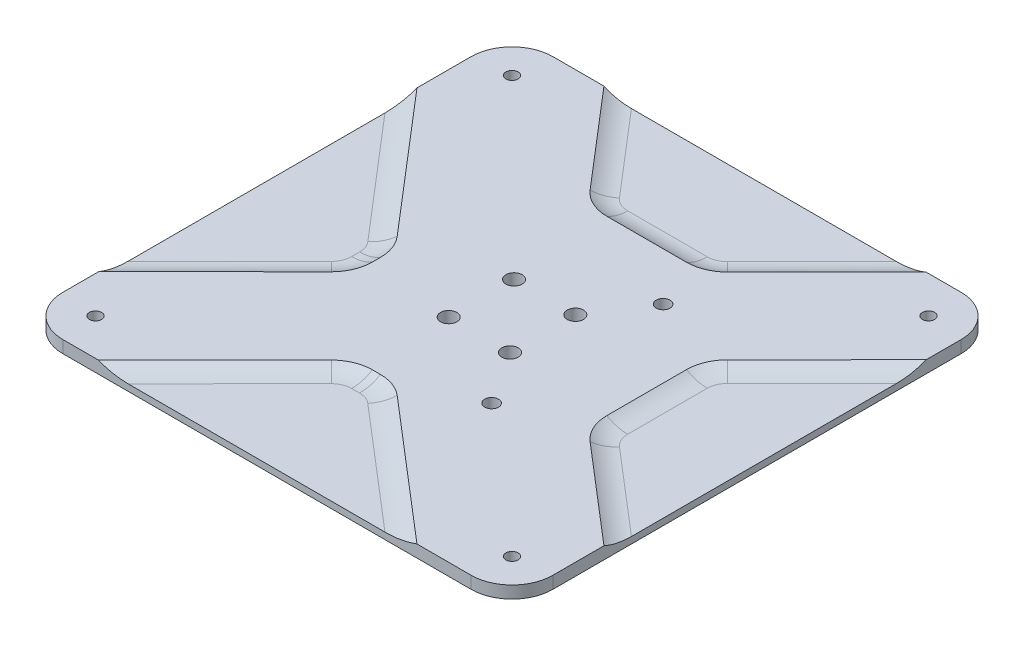
SolidWorks part; units mm, degrees
material "ABS"
ref_plane "Alzado" through (0, 0, 0) normal (0, 0, 1) x (1, 0, 0)
ref_plane "Planta" through (0, 0, 0) normal (0, 1, 0) x (1, 0, 0)
ref_plane "Vista lateral" through (0, 0, 0) normal (1, 0, 0) x (0, 0, -1)
sketch "Sketch1" plane through (0, 0, 0) normal (0, 1, 0) x (1, 0, 0)
  line L1 (-7.5, -8) -> (7.5, -8) construction
  line L2 (-7.5, -8) -> (-7.5, 8) construction
  line L3 (-7.5, 8) -> (7.5, 8) construction
  line L4 (7.5, -8) -> (7.5, 8) construction
  line L5 (-7.5, -8) -> (7.5, 8) construction
  line L6 (-7.5, 8) -> (7.5, -8) construction
  line L7 (-60, -60) -> (60, -60)
  line L8 (-60, -60) -> (-60, 60)
  line L9 (-60, 60) -> (60, 60)
  line L10 (60, -60) -> (60, 60)
  circle A0 centre (-7.5, -8) radius 2
  circle A1 centre (7.5, 8) radius 2
  circle A2 centre (7.5, -8) radius 2
  circle A3 centre (-7.5, 8) radius 2
  point P0 (0, 0)
  point P10 (0, 0)
  point P16 (-60, 0)
  point P17 (0, -60)
  dimension "D3" = 4
  dimension "D1" = 16
  dimension "D2" = 15
  dimension "D4" = 120
  dimension "D5" = 120
extrude "Boss-Extrude1" add sketch "Sketch1" along normal blind 3
fillet "Fillet1" radius 10 4 edges at (-60, 1.5, -60) (60, 1.5, -60) (60, 1.5, 60) (-60, 1.5, 60)
sketch "Sketch2" plane through (0, 3, 0) normal (0, 1, 0) x (1, 0, 0)
  line L0 (50, 60) -> (-50, 60) construction
  line L1 (-60, 50) -> (-60, -50) construction
  circle A0 centre (-51, 51) radius 1.5
  dimension "D1" = 3
  dimension "D2" = 9
  dimension "D3" = 9
extrude "Cut-Extrude1" cut sketch "Sketch2" against normal through all
mirror "Mirror3" about plane through (0, 0, 0) normal (0, 0, 1) of "Cut-Extrude1" second plane through (0, 0, 0) second plane normal (1, 0, 0)
sketch "Sketch3" plane through (0, 3, 0) normal (0, 1, 0) x (1, 0, 0)
  line L0 (16, 21) -> (16, -21) construction
  circle A2 centre (16, 21) radius 1.7
  circle A3 centre (16, -21) radius 1.7
  point P4 (16, 0)
  dimension "D2" = 42
  dimension "D1" = 3.4
  dimension "D3" = 16
extrude "Cut-Extrude2" cut sketch "Sketch3" against normal through all
sketch "Sketch5" plane through (0, 3, 0) normal (0, 1, 0) x (1, 0, 0)
  line L0 (60, 41.4316) -> (32.7473, 14.122)
  line L1 (60, -50) -> (60, 50) construction
  line L2 (32.7473, 14.122) -> (32.7473, -14.122)
  line L3 (32.7473, -14.122) -> (60, -37.4814)
  line L4 (0, 60) -> (0, -60) construction
  line L5 (60, 41.4316) -> (60, -37.4814)
  line L6 (-50, -60) -> (50, -60) construction
  line L7 (36.7283, -60) -> (0, -28.5186)
  line L8 (0, -28.5186) -> (-9.8043, -28.5186)
  line L9 (-9.8043, -28.5186) -> (-41.22, -60)
  line L10 (-60, 0) -> (60, 0) construction
  line L11 (-41.22, -60) -> (36.7283, -60)
  line L12 (16, -21) -> (51, -51) construction
  line L13 (16, 21) -> (16, -21) construction
  line L14 (0, -28.5186) -> (9.8043, -28.5186) construction
  line L15 (9.8043, -28.5186) -> (9.8043, -36.9222) construction
  line L16 (60, -37.4814) -> (36.7283, -60) construction
  line L17 (57.0711, 57.0711) -> (-58.3189, -58.3189) construction
  line L18 (-60, -41.22) -> (-60, 36.7283)
  line L19 (-28.5186, -9.8043) -> (-60, -41.22)
  line L20 (-28.5186, 0) -> (-28.5186, -9.8043)
  line L21 (-60, 36.7283) -> (-28.5186, 0)
  line L22 (41.4316, 60) -> (-37.4814, 60)
  line L23 (-14.122, 32.7473) -> (-37.4814, 60)
  line L24 (14.122, 32.7473) -> (-14.122, 32.7473)
  line L25 (41.4316, 60) -> (14.122, 32.7473)
  arc A0 (60, 50) -> (50, 60) centre (50, 50) ccw construction
  point P18 (48.3642, -48.7407)
  point P20 (32.7473, 0)
extrude "Cut-Extrude3" cut sketch "Sketch5" against normal blind 1.4
fillet "Fillet2" radius 10 8 edges at (-28.5186, 2.3, 9.8043) (-28.5186, 2.3, 0) (-14.122, 2.3, -32.7473) (14.122, 2.3, -32.7473) (32.7473, 2.3, 14.122) (32.7473, 2.3, -14.122) (0, 2.3, 28.5186) (-9.8043, 2.3, 28.5186)
fillet "Fillet3" radius 10 20 edges at (-45.7274, 1.6, 26.9773) (-29.2818, 1.6, 9.4877) (-28.5186, 1.6, 4.6776) (-45.463, 1.6, -19.7685) (19.7685, 1.6, 45.463) (-0.2298, 1.6, 29.1397) (-4.6776, 1.6, 28.5186) (-26.9773, 1.6, 45.7274) (-27.2983, 1.6, -48.1197) (-13.7012, 1.6, -33.6622) (29.2407, 1.6, -47.8344) (13.808, 1.6, -33.5065) (48.1197, 1.6, 27.2983) (33.6622, 1.6, 13.7012) (32.7473, 1.6, -0.2317) (33.5065, 1.6, -13.808) (-29.1397, 1.6, 0.2298) (-9.4877, 1.6, 29.2818) (0.2317, 1.6, -32.7473) (47.8344, 1.6, -29.2407)
